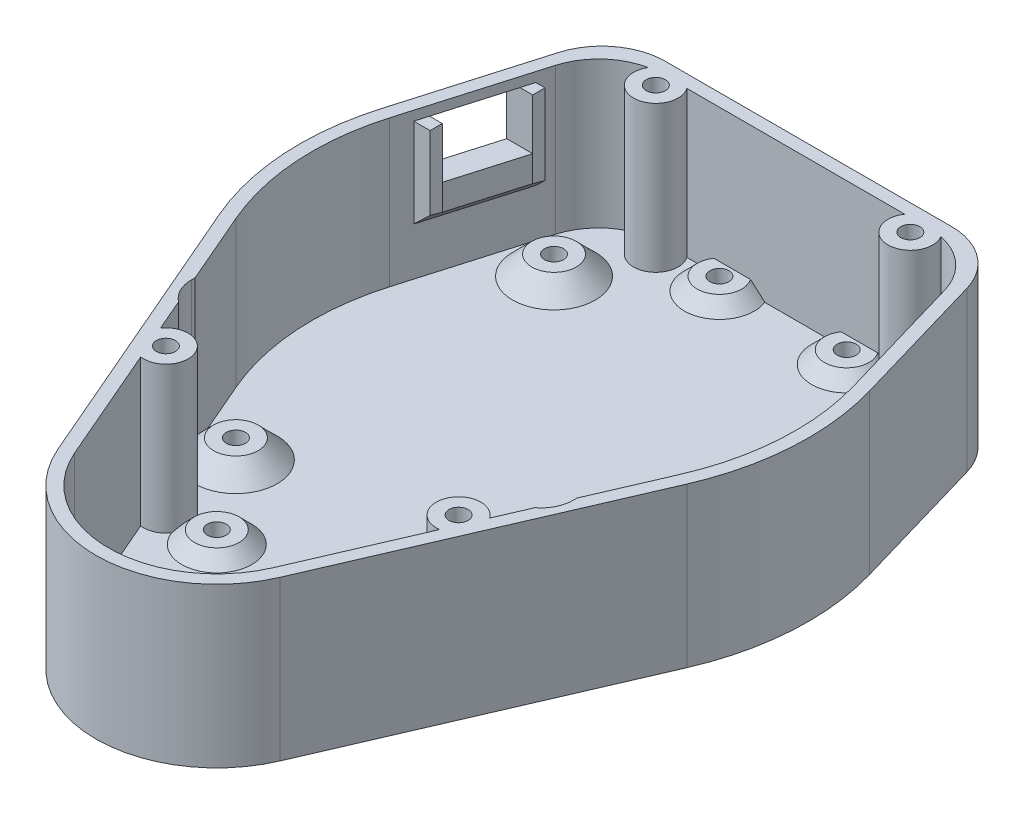
SolidWorks part; units mm, degrees
material "PET"
ref_plane "Front Plane" through (0, 0, 0) normal (0, 0, 1) x (1, 0, 0)
ref_plane "Top Plane" through (0, 0, 0) normal (0, 1, 0) x (1, 0, 0)
ref_plane "Right Plane" through (0, 0, 0) normal (1, 0, 0) x (0, 0, -1)
sketch "Sketch1" plane through (0, 37.073, 0) normal (0, -1, 0) x (1, 0, 0)
  line L85 (-17.1277, -38) -> (17.1277, -38)
  line L86 (30.6, -30.8) -> (36.48, -10.64)
  line L87 (34.8898, 15.0566) -> (25.8596, 35.9819)
  line L88 (-15.6086, 59.7358) -> (-23.4933, 41.4651)
  line L89 (-36.48, -10.64) -> (-30.6, -30.8)
  line L90 (-17.1277, -38) -> (17.1277, -38)
  line L91 (30.6, -30.8) -> (36.48, -10.64)
  line L92 (34.8898, 15.0566) -> (25.8596, 35.9819)
  line L93 (-15.6086, 59.7358) -> (-23.4933, 41.4651)
  line L94 (-36.48, -10.64) -> (-30.6, -30.8)
  line L100 (-22.5, -40) -> (22.5, -40)
  line L101 (32.1, -32.8) -> (38.4, -11.2)
  line L102 (36.7261, 15.8491) -> (17.4449, 60.5283)
  line L103 (-17.4449, 60.5283) -> (-36.7261, 15.8491)
  line L104 (-38.4, -11.2) -> (-32.1, -32.8)
  line L105 (-22.5, -40) -> (22.5, -40)
  line L106 (32.1, -32.8) -> (38.4, -11.2)
  line L107 (36.7261, 15.8491) -> (17.4449, 60.5283)
  line L108 (-17.4449, 60.5283) -> (-36.7261, 15.8491)
  line L109 (-38.4, -11.2) -> (-32.1, -32.8)
  line L149 (23.4933, 41.4651) -> (15.6086, 59.7358)
  line L150 (23.4933, 41.4651) -> (15.6086, 59.7358)
  line L151 (-25.8596, 35.9819) -> (-34.8898, 15.0566)
  line L152 (-25.8596, 35.9819) -> (-34.8898, 15.0566)
  arc A66 (23.0033, -37.7973) -> (30.6, -30.8) centre (21, -28) ccw
  arc A68 (36.48, -10.64) -> (34.8898, 15.0566) centre (0, 0) ccw
  arc A69 (15.6086, 59.7358) -> (-15.6086, 59.7358) centre (0, 53) ccw
  arc A70 (-34.8898, 15.0566) -> (-36.48, -10.64) centre (0, 0) ccw
  arc A71 (-30.6, -30.8) -> (-23.0033, -37.7973) centre (-21, -28) ccw
  arc A72 (23.0033, -37.7973) -> (30.6, -30.8) centre (21, -28) ccw
  arc A73 (36.48, -10.64) -> (34.8898, 15.0566) centre (0, 0) ccw
  arc A74 (15.6086, 59.7358) -> (-15.6086, 59.7358) centre (0, 53) ccw
  arc A75 (-34.8898, 15.0566) -> (-36.48, -10.64) centre (0, 0) ccw
  arc A76 (-30.6, -30.8) -> (-23.0033, -37.7973) centre (-21, -28) ccw
  arc A82 (22.5, -40) -> (32.1, -32.8) centre (22.5, -30) ccw
  arc A83 (38.4, -11.2) -> (36.7261, 15.8491) centre (0, 0) ccw
  arc A84 (17.4449, 60.5283) -> (-17.4449, 60.5283) centre (0, 53) ccw
  arc A85 (-36.7261, 15.8491) -> (-38.4, -11.2) centre (0, 0) ccw
  arc A86 (-32.1, -32.8) -> (-22.5, -40) centre (-22.5, -30) ccw
  arc A87 (22.5, -40) -> (32.1, -32.8) centre (22.5, -30) ccw
  arc A88 (38.4, -11.2) -> (36.7261, 15.8491) centre (0, 0) ccw
  arc A89 (17.4449, 60.5283) -> (-17.4449, 60.5283) centre (0, 53) ccw
  arc A90 (-36.7261, 15.8491) -> (-38.4, -11.2) centre (0, 0) ccw
  arc A91 (-32.1, -32.8) -> (-22.5, -40) centre (-22.5, -30) ccw
  arc A135 (23.0033, -37.7973) -> (17.1277, -38) centre (20, -36) ccw
  arc A136 (23.0033, -37.7973) -> (17.1277, -38) centre (20, -36) ccw
  arc A137 (23.4933, 41.4651) -> (25.8596, 35.9819) centre (23, 38) ccw
  arc A138 (23.4933, 41.4651) -> (25.8596, 35.9819) centre (23, 38) ccw
  arc A139 (-25.8596, 35.9819) -> (-23.4933, 41.4651) centre (-23, 38) ccw
  arc A140 (-25.8596, 35.9819) -> (-23.4933, 41.4651) centre (-23, 38) ccw
  arc A141 (-17.1277, -38) -> (-23.0033, -37.7973) centre (-20, -36) ccw
  arc A142 (-17.1277, -38) -> (-23.0033, -37.7973) centre (-20, -36) ccw
  dimension "D1" = 0
  dimension "D2" = 0
extrude "Boss-Extrude1" add sketch "Sketch1" along normal blind 25
sketch "Sketch2" plane through (0, 12.073, 0) normal (0, -1, 0) x (1, 0, 0)
  line L10 (-38.4, -11.2) -> (-32.1, -32.8)
  line L11 (-22.5, -40) -> (22.5, -40)
  line L12 (32.1, -32.8) -> (38.4, -11.2)
  line L13 (36.7261, 15.8491) -> (17.4449, 60.5283)
  line L14 (-17.4449, 60.5283) -> (-36.7261, 15.8491)
  line L15 (-38.4, -11.2) -> (-32.1, -32.8)
  line L16 (-22.5, -40) -> (22.5, -40)
  line L17 (32.1, -32.8) -> (38.4, -11.2)
  line L18 (36.7261, 15.8491) -> (17.4449, 60.5283)
  line L19 (-17.4449, 60.5283) -> (-36.7261, 15.8491)
  arc A10 (-32.1, -32.8) -> (-22.5, -40) centre (-22.5, -30) ccw
  arc A11 (22.5, -40) -> (32.1, -32.8) centre (22.5, -30) ccw
  arc A12 (38.4, -11.2) -> (36.7261, 15.8491) centre (0, 0) ccw
  arc A13 (17.4449, 60.5283) -> (-17.4449, 60.5283) centre (0, 53) ccw
  arc A14 (-36.7261, 15.8491) -> (-38.4, -11.2) centre (0, 0) ccw
  arc A15 (-32.1, -32.8) -> (-22.5, -40) centre (-22.5, -30) ccw
  arc A16 (22.5, -40) -> (32.1, -32.8) centre (22.5, -30) ccw
  arc A17 (38.4, -11.2) -> (36.7261, 15.8491) centre (0, 0) ccw
  arc A18 (17.4449, 60.5283) -> (-17.4449, 60.5283) centre (0, 53) ccw
  arc A19 (-36.7261, 15.8491) -> (-38.4, -11.2) centre (0, 0) ccw
  dimension "D1" = 0
extrude "Boss-Extrude2" add sketch "Sketch2" against normal blind 2
sketch "Sketch3" plane through (0, 14.073, 0) normal (0, 1, 0) x (1, 0, 0)
  circle A0 centre (-25, 25) radius 1.5
  circle A1 centre (25, 25) radius 1.5
  circle A2 centre (25, -25) radius 1.5
  circle A3 centre (-25, -25) radius 1.5
  circle A4 centre (25, -25) radius 3.5
  circle A5 centre (25, 25) radius 3.5
  circle A6 centre (-25, 25) radius 3.5
  circle A7 centre (-25, -25) radius 3.5
  dimension "D1" = 3
  dimension "D2" = 2
  dimension "D3" = 2
  dimension "D4" = 2
  dimension "D5" = 2
extrude "Boss-Extrude3" add sketch "Sketch3" along normal blind 3
sketch "Sketch4" plane through (0, 14.073, 0) normal (0, 1, 0) x (1, 0, 0)
  line L0 (-25, -32) -> (25, -32)
  line L4 (-30, 27) -> (-30, -27)
  line L5 (-30, 27) -> (-30, -27)
  line L8 (30, -27) -> (30, 27)
  line L9 (30, -27) -> (30, 27)
  line L12 (25, 32) -> (-25, 32)
  line L13 (25, 32) -> (-25, 32)
  arc A2 (-30, -27) -> (-25, -32) centre (-25, -27) ccw
  arc A3 (-30, -27) -> (-25, -32) centre (-25, -27) ccw
  arc A5 (25, -32) -> (30, -27) centre (25, -27) ccw
  arc A6 (25, -32) -> (30, -27) centre (25, -27) ccw
  arc A12 (30, 27) -> (25, 32) centre (25, 27) ccw
  arc A13 (-25, 32) -> (-30, 27) centre (-25, 27) ccw
  arc A14 (30, 27) -> (25, 32) centre (25, 27) ccw
  arc A15 (-25, 32) -> (-30, 27) centre (-25, 27) ccw
  circle A16 centre (-25, -25) radius 3.5
  circle A17 centre (-25, -25) radius 3.5
  circle A19 centre (-25, 25) radius 3.5
  circle A20 centre (-25, 25) radius 3.5
  circle A22 centre (25, 25) radius 3.5
  circle A23 centre (25, 25) radius 3.5
  circle A25 centre (25, -25) radius 3.5
  circle A26 centre (25, -25) radius 3.5
  circle M13 centre (-25, -25) radius 3.5
  circle M14 centre (-25, 25) radius 3.5
  circle M15 centre (25, 25) radius 3.5
  circle M16 centre (25, -25) radius 3.5
  line M19 (-23.4933, -41.4651) -> (-15.6086, -59.7358)
  line M21 (25.8596, -35.9819) -> (34.8898, -15.0566)
  dimension "D1" = 0
  dimension "D2" = 0
  dimension "D3" = 0
  dimension "D4" = 0
  dimension "D5" = 0
  dimension "D6" = 0
  dimension "D7" = 0
extrude "Cut-Extrude1" cut sketch "Sketch4" along normal up to surface (23 mm away) contours L13 A15 L5 A3 L0 A6 L9 A14 M19 M21 M14 M16 M15 M13 | L5 A3 M19 | A6 L9 M21 region at (-0.0174, 14.073, -0.0172) region at (29.2352, 14.073, 28.8201) up to face at (0, 37.073, -0.6681)
sketch "Sketch6" plane through (0, 37.073, 0) normal (0, 1, 0) x (1, 0, 0)
  circle A0 centre (-20, 36) radius 1.5
  circle A1 centre (20, 36) radius 1.5
  circle A2 centre (23, -38) radius 1.5
  circle A3 centre (-23, -38) radius 1.5
  dimension "D1" = 3
  dimension "D2" = 3
  dimension "D3" = 3
  dimension "D4" = 3
extrude "Cut-Extrude3" cut sketch "Sketch6" against normal blind 5
sketch "Sketch7" plane through (0, 0, 0) normal (1, 0, 0) x (0, 0, -1)
  line L1 (25, 29.073) -> (17, 29.073)
  line L2 (25, 29.073) -> (25, 34.073)
  line L3 (25, 34.073) -> (17, 34.073)
  line L4 (17, 29.073) -> (17, 34.073)
  line L5 (25, 29.073) -> (17, 34.073) construction
  line L6 (25, 34.073) -> (17, 29.073) construction
  line L10 (32, 17.073) -> (-32, 17.073)
  line L11 (-32, 17.073) -> (-32, 18.673)
  line L12 (-32, 18.673) -> (32, 18.673)
  line L13 (32, 18.673) -> (32, 17.073)
  line L15 (26.5, 27.573) -> (15.5, 27.573)
  line L16 (26.5, 27.573) -> (26.5, 35.573)
  line L17 (26.5, 35.573) -> (15.5, 35.573)
  line L18 (15.5, 27.573) -> (15.5, 35.573)
  line L19 (26.5, 27.573) -> (15.5, 35.573) construction
  line L20 (26.5, 35.573) -> (15.5, 27.573) construction
  point P0 (21, 31.573)
  point P7 (21, 31.573)
  dimension "D1" = 17
  dimension "D2" = 7
  dimension "D3" = 5
  dimension "D4" = 8
  dimension "D5" = 8
  dimension "D6" = 11
extrude "Cut-Extrude4" cut sketch "Sketch7" against normal through all contours L4 L1 L2 L3 | L18 L15 L16 L17 L1 L4 L3 L2 region at (0, 31.573, -21) region at (0, 27.709, -21)
sketch "Sketch9" plane through (0, 27.573, 0) normal (0, 1, 0) x (1, 0, 0)
  line L0 (-35.0625, 15.5) -> (-31.8542, 26.5)
  line L1 (-31.8542, 26.5) -> (-29.8542, 26.5)
  line L2 (-29.8542, 26.5) -> (-29.8542, 28.42)
  line L3 (-29.8542, 28.42) -> (-31.2942, 28.42)
  line L4 (-36.48, 10.64) -> (-30.6, 30.8) construction
  line L5 (-31.2942, 28.42) -> (-31.8542, 26.5)
  line L6 (-35.0625, 15.5) -> (-35.6225, 13.58)
  line L7 (-35.6225, 13.58) -> (-33.0625, 13.58)
  line L8 (-33.0625, 13.58) -> (-33.0625, 15.5)
  line L9 (-33.0625, 15.5) -> (-35.0625, 15.5)
  dimension "D1" = 2
  dimension "D2" = 2
  dimension "D3" = 2
  dimension "D4" = 2
extrude "Boss-Extrude5" add sketch "Sketch9" along normal blind 8 contours L8 L9 L6 L7 | L3 L5 L1 L2 region at (-30.7218, 27.573, -27.4079) region at (-34.2082, 27.573, -14.5007)
sketch "Sketch10" plane through (0, 27.573, 0) normal (0, -1, 0) x (1, 0, 0)
  line L0 (-35.6225, -13.58) -> (-31.2942, -28.42)
  line L1 (-31.2942, -28.42) -> (-29.8542, -28.42)
  line L2 (-29.8542, -28.42) -> (-29.8542, -26.5)
  line L3 (-29.8542, -26.5) -> (-33.0625, -15.5)
  line L4 (-33.0625, -15.5) -> (-33.0625, -13.58)
  line L5 (-33.0625, -13.58) -> (-35.6225, -13.58)
extrude "Boss-Extrude6" add sketch "Sketch10" along normal blind 3
chamfer "Chamfer1" distance 3 angle 45 1 edges at (-33.4583, 24.573, -21)
sketch "Sketch11" plane through (0, 12.073, 0) normal (0, -1, 0) x (1, 0, 0)
  circle A5 centre (10, -36) radius 1.5
  circle A6 centre (-10, -36) radius 1.5
  circle A7 centre (15, 38) radius 1.5
  circle A8 centre (-15, 38) radius 1.5
extrude "Cut-Extrude5" cut sketch "Sketch11" against normal blind 10
sketch "Sketch12" plane through (0, 14.073, 0) normal (0, 1, 0) x (1, 0, 0)
  circle A2 centre (-10, 36) radius 1.5
  circle A3 centre (-10, 36) radius 1.5
  circle A16 centre (10, 36) radius 1.5
  circle A17 centre (10, 36) radius 1.5
  circle A30 centre (-15, -38) radius 1.5
  circle A31 centre (-15, -38) radius 1.5
  circle A32 centre (-15, -38) radius 3.5
  circle A33 centre (15, -38) radius 1.5
  circle A34 centre (15, -38) radius 1.5
  circle A35 centre (15, -38) radius 3.5
  circle A36 centre (10, 36) radius 3.5
  circle A37 centre (-10, 36) radius 3.5
  dimension "D1" = 0
  dimension "D2" = 0
  dimension "D3" = 0
  dimension "D4" = 0
  dimension "D5" = 2
  dimension "D6" = 2
  dimension "D7" = 2
  dimension "D8" = 2
extrude "Boss-Extrude7" add sketch "Sketch12" along normal blind 2
chamfer "Chamfer2" distance 2 angle 45 4 edges at (-11.5, 14.073, 38) (18.5, 14.073, 38) (10, 14.073, -32.5) (-10, 14.073, -32.5)
chamfer "Chamfer3" distance 3 angle 45 4 edges at (28.5, 14.073, 25) (-21.5, 14.073, 25) (-21.5, 14.073, -25) (28.5, 14.073, -25)
